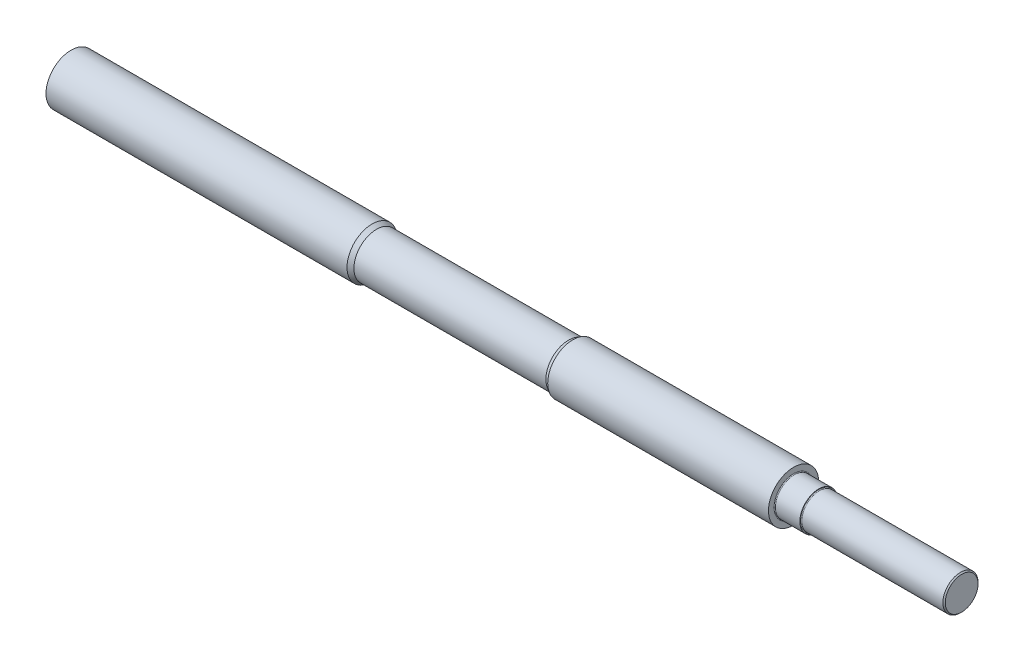
SolidWorks part; units mm, degrees
ref_plane "前视基准面" through (0, 0, 0) normal (0, 0, 1) x (1, 0, 0)
ref_plane "上视基准面" through (0, 0, 0) normal (0, 1, 0) x (1, 0, 0)
ref_plane "右视基准面" through (0, 0, 0) normal (1, 0, 0) x (0, 0, -1)
sketch "草图1" plane through (0, 0, 0) normal (0, 0, 1) x (1, 0, 0)
  line L0 (288, 0) -> (288, 7.8)
  line L1 (288.3, 7.5) -> (298, 7.5)
  line L2 (298, 7.5) -> (298, 7.3)
  line L3 (298.3, 7) -> (354.5333, 7)
  line L4 (354.5333, 7) -> (355, 6.5333)
  line L5 (355, 6.5333) -> (355, 0)
  line L6 (355, 0) -> (288, 0)
  line L7 (355, 0) -> (288, 0) construction
  arc A0 (288, 7.8) -> (288.3, 7.5) centre (288.3, 7.8) ccw
  arc A1 (298, 7.3) -> (298.3, 7) centre (298.3, 7.3) ccw
revolve "旋转1" add sketch "草图1" angle 360 about L7 reverse direction yes
sketch "草图2" plane through (0, 0, 0) normal (0, 0, 1) x (1, 0, 0)
  line L0 (0, 0) -> (0, 10)
  line L1 (0, 10) -> (120, 10)
  line L2 (120, 10) -> (121.7321, 9)
  line L3 (121.7321, 9) -> (198.2679, 9)
  line L4 (198.2679, 9) -> (200, 10)
  line L5 (200, 10) -> (288, 10)
  line L6 (288, 10) -> (288, 0)
  line L7 (288, 0) -> (0, 0)
  line L8 (288, 0) -> (0, 0) construction
  point P8 (0, 0)
  point P9 (0, 0)
  point P11 (0, 0)
  point P13 (0, 0)
revolve "旋转2" add sketch "草图2" angle 360 about L8 reverse direction yes
cosmetic thread "装饰螺纹线1" parameters "D1"=120, "D2"=15.5
cosmetic thread "装饰螺纹线2" parameters "D1"=88, "D2"=15.5
sketch "草图3" plane through (0, 0, 0) normal (0, 0, 1) x (1, 0, 0)
  line L0 (0, 0) -> (0, 5)
  line L1 (0, 5) -> (0.812, 4.188)
  line L2 (0.812, 4.188) -> (24, 4.188)
  line L3 (24, 4.188) -> (26.4179, 0)
  line L4 (26.4179, 0) -> (0, 0)
  line L5 (26.4179, 0) -> (0, 0) construction
revolve "切除-旋转1" cut sketch "草图3" angle 360 about L5 reverse direction yes
cosmetic thread "装饰螺纹线3"
ref_plane "基准面4" through (177.5, 0, 0) normal (1, 0, 0) x (0, 0, -1)
ref_plane "基准面5" through (288, 0, 0) normal (1, 0, 0) x (0, 0, -1)
ref_plane "基准面6" through (355, 0, 0) normal (1, 0, 0) x (0, 0, -1)
ref_plane "to_kue XY" through (177.5, 0, 0) normal (1, 0, 0) x (0, 0, -1)
ref_plane "to_kue XZ" through (0, 0, 0) normal (0, -1, 0) x (-1, 0, 0)
ref_plane "to_kue YZ" through (0, 0, 0) normal (0, 0, -1) x (-1, 0, 0)
ref_axis "to_kue X" through (177.5, 0, 80.9) along (0, 0, -1)
ref_axis "to_kue Y" through (177.5, -50, 0) along (0, 1, 0)
ref_axis "to_kue Z" through (80.9, 0, 0) along (-1, 0, 0)
sketch3d "to_kue"
  point P0 (177.5, 0, 0)
ref_plane "to_kue2 XY" through (0, 0, 0) normal (1, 0, 0) x (0, 0, -1)
ref_plane "to_kue2 XZ" through (0, 0, 0) normal (0, -1, 0) x (-1, 0, 0)
ref_plane "to_kue2 YZ" through (0, 0, 0) normal (0, 0, -1) x (-1, 0, 0)
ref_axis "to_kue2 X" through (0, 0, 80.9) along (0, 0, -1)
ref_axis "to_kue2 Y" through (0, -50, 0) along (0, 1, 0)
ref_axis "to_kue2 Z" through (80.9, 0, 0) along (-1, 0, 0)
sketch3d "to_kue2"
  point P0 (0, 0, 0)
ref_plane "to_frame XY" through (288, 0, 0) normal (1, 0, 0) x (0, 0, -1)
ref_plane "to_frame XZ" through (0, 0, 0) normal (0, -1, 0) x (-1, 0, 0)
ref_plane "to_frame YZ" through (0, 0, 0) normal (0, 0, -1) x (-1, 0, 0)
ref_axis "to_frame X" through (288, 0, 80.9) along (0, 0, -1)
ref_axis "to_frame Y" through (288, -50, 0) along (0, 1, 0)
ref_axis "to_frame Z" through (80.9, 0, 0) along (-1, 0, 0)
sketch3d "to_frame"
  point P0 (288, 0, 0)
ref_plane "to_washer2 XY" through (355, 0, 0) normal (1, 0, 0) x (0, 0, -1)
ref_plane "to_washer2 XZ" through (0, 0, 0) normal (0, -1, 0) x (-1, 0, 0)
ref_plane "to_washer2 YZ" through (0, 0, 0) normal (0, 0, -1) x (-1, 0, 0)
ref_axis "to_washer2 X" through (355, 0, 80.9) along (0, 0, -1)
ref_axis "to_washer2 Y" through (355, -50, 0) along (0, 1, 0)
ref_axis "to_washer2 Z" through (80.9, 0, 0) along (-1, 0, 0)
sketch3d "to_washer2"
  point P0 (355, 0, 0)
ref_plane "to_handwheel XY" through (355, 0, 0) normal (-1, 0, 0) x (0, 0, 1)
ref_plane "to_handwheel XZ" through (0, 0, 0) normal (0, 1, 0) x (1, 0, 0)
ref_plane "to_handwheel YZ" through (0, 0, 0) normal (0, 0, -1) x (-1, 0, 0)
ref_axis "to_handwheel X" through (355, 0, 80.9) along (0, 0, -1)
ref_axis "to_handwheel Y" through (355, 50, 0) along (0, -1, 0)
ref_axis "to_handwheel Z" through (-80.9, 0, 0) along (1, 0, 0)
sketch3d "to_handwheel"
  point P0 (355, 0, 0)
ref_plane "to_washer XY" through (0, 0, 0) normal (1, 0, 0) x (0, 0, -1)
ref_plane "to_washer XZ" through (0, 0, 0) normal (0, -1, 0) x (-1, 0, 0)
ref_plane "to_washer YZ" through (0, 0, 0) normal (0, 0, -1) x (-1, 0, 0)
ref_axis "to_washer X" through (0, 0, 80.9) along (0, 0, -1)
ref_axis "to_washer Y" through (0, -50, 0) along (0, 1, 0)
ref_axis "to_washer Z" through (80.9, 0, 0) along (-1, 0, 0)
sketch3d "to_washer"
  point P0 (0, 0, 0)
